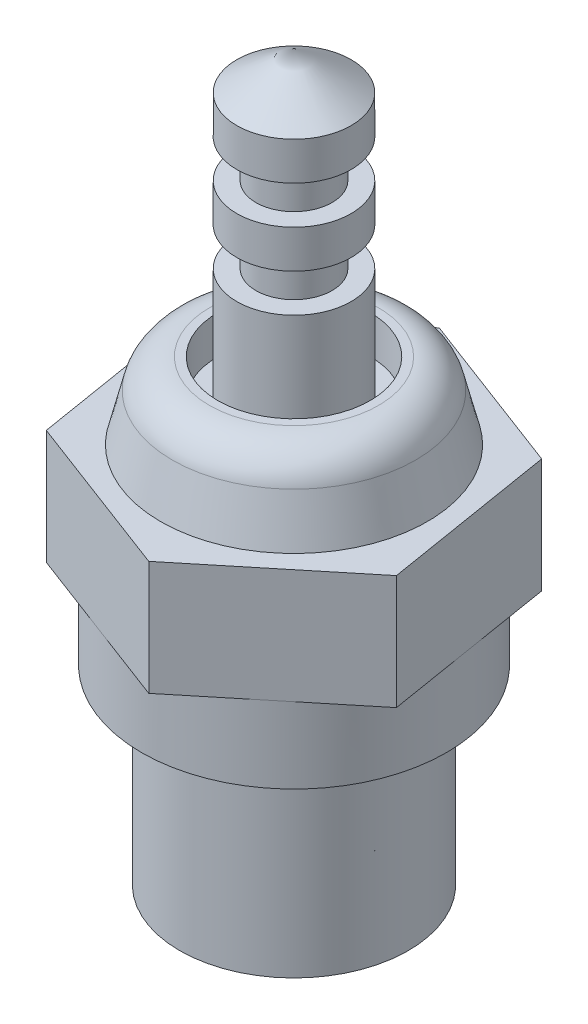
SolidWorks part; units mm, degrees
material "Nickel"
ref_plane "Front" through (0, 0, 0) normal (0, 0, 1) x (1, 0, 0)
ref_plane "Top" through (0, 0, 0) normal (0, 1, 0) x (1, 0, 0)
ref_plane "Right" through (0, 0, 0) normal (1, 0, 0) x (0, 0, -1)
sketch "Sketch1" plane through (0, 0, 0) normal (0, 1, 0) x (1, 0, 0)
  circle A0 centre (0, 0) radius 3
  dimension "D1" = 6
extrude "Boss-Extrude1" add sketch "Sketch1" along normal blind 5
cosmetic thread "Cosmetic Thread1" parameters "D1"=4, "D2"=4.891
sketch "Sketch2" plane through (0, 5, 0) normal (0, 1, 0) x (1, 0, 0)
  circle A0 centre (0, 0) radius 4
  dimension "D1" = 8
extrude "Boss-Extrude2" add sketch "Sketch2" along normal blind 2
sketch "Sketch3" plane through (0, 7, 0) normal (0, 1, 0) x (1, 0, 0)
  line L1 (0.7467, -4.558) -> (4.3207, -1.6324)
  line L2 (4.3207, -1.6324) -> (3.574, 2.9257)
  line L3 (3.574, 2.9257) -> (-0.7467, 4.558)
  line L4 (-0.7467, 4.558) -> (-4.3207, 1.6324)
  line L5 (-4.3207, 1.6324) -> (-3.574, -2.9257)
  line L6 (-3.574, -2.9257) -> (0.7467, -4.558)
  circle A0 centre (0, 0) radius 4 construction
extrude "Boss-Extrude3" add sketch "Sketch3" along normal blind 3
sketch "Sketch4" plane through (0, 10, 0) normal (0, 1, 0) x (1, 0, 0)
  circle A0 centre (0, 0) radius 3.5
  dimension "D1" = 7
extrude "Boss-Extrude4" add sketch "Sketch4" along normal blind 2 draft 14
sketch "Sketch6" plane through (0, 12, 0) normal (0, 1, 0) x (1, 0, 0)
  circle A0 centre (0, 0) radius 2
  dimension "D1" = 4
extrude "Cut-Extrude2" cut sketch "Sketch6" against normal blind 1
sketch "Sketch7" plane through (0, 0, 0) normal (0, -1, 0) x (-1, 0, 0)
  circle A0 centre (0, 0) radius 1.5
extrude "Cut-Extrude3" cut sketch "Sketch7" against normal through all
ref_plane "Plane2" through (0, 0, 0) normal (0.9868, 0, -0.1617) x (-0.1617, 0, -0.9868)
fillet "Fillet1" radius 1 1 edges at (0, 12, 3.0013)
ref_plane "Plane3" through (0, 10, 0) normal (0, 1, 0) x (1, 0, 0)
sketch "Sketch16" plane through (0, 10, 0) normal (0, 1, 0) x (1, 0, 0)
  circle A0 centre (0, 0) radius 1.5
extrude "Boss-Extrude10" add sketch "Sketch16" along normal blind 4
sketch "Sketch17" plane through (0, 14, 0) normal (0, 1, 0) x (1, 0, 0)
  circle A0 centre (0, 0) radius 1
extrude "Boss-Extrude11" add sketch "Sketch17" along normal blind 1
sketch "Sketch18" plane through (0, 15, 0) normal (0, 1, 0) x (1, 0, 0)
  circle A0 centre (0, 0) radius 1.5
extrude "Boss-Extrude12" add sketch "Sketch18" along normal blind 1
sketch "Sketch21" plane through (0, 16, 0) normal (0, 1, 0) x (1, 0, 0)
  circle A0 centre (0, 0) radius 1
extrude "Boss-Extrude13" add sketch "Sketch21" along normal blind 1
sketch "Sketch22" plane through (0, 17, 0) normal (0, 1, 0) x (1, 0, 0)
  circle A0 centre (0, 0) radius 1.5
extrude "Boss-Extrude14" add sketch "Sketch22" along normal blind 1
sketch "Sketch23" plane through (0, 0, 0) normal (0.9868, 0, -0.1617) x (-0.1617, 0, -0.9868)
  line L0 (0, 14.4092) -> (0, 20.5822) construction
  line L1 (0, 18) -> (0, 19)
  line L2 (1.5, 18) -> (-1.5, 18) construction
  line L3 (0, 19) -> (-1.5, 18)
  line L4 (-1.5, 18) -> (0, 18)
  dimension "D1" = 1
revolve "Revolve4" add sketch "Sketch23" angle 360 about L1
sketch "Sketch24" plane through (0, 10, 0) normal (0, -1, 0) x (1, 0, 0)
  circle A0 centre (0, 0) radius 0.5
curve "Helix/Spiral3" pitch 0.2956 height 10.0504 turns 34
ref_plane "Plane5" through (0, 0, 0) normal (0.6334, 0, 0.7738) x (0.7738, 0, -0.6334)
sketch "Sketch27" plane through (0, 0, 0) normal (0.6334, 0, 0.7738) x (0.7738, 0, -0.6334)
  circle A0 centre (-0.5, -0.0457) radius 0.05
sweep "Sweep1" add profiles "Sketch27" path "Helix/Spiral3"
ref_plane "Plane6" through (0, 0, 0) normal (0.6334, 0, 0.7738) x (0.7738, 0, -0.6334)
sketch "Sketch33" plane through (0, 0, 0) normal (0.7071, 0, 0.7071) x (0.7071, 0, -0.7071)
  circle A0 centre (-0.5, -0.0508) radius 0.0496
extrude "Boss-Extrude15" add sketch "Sketch33" along normal blind 2
